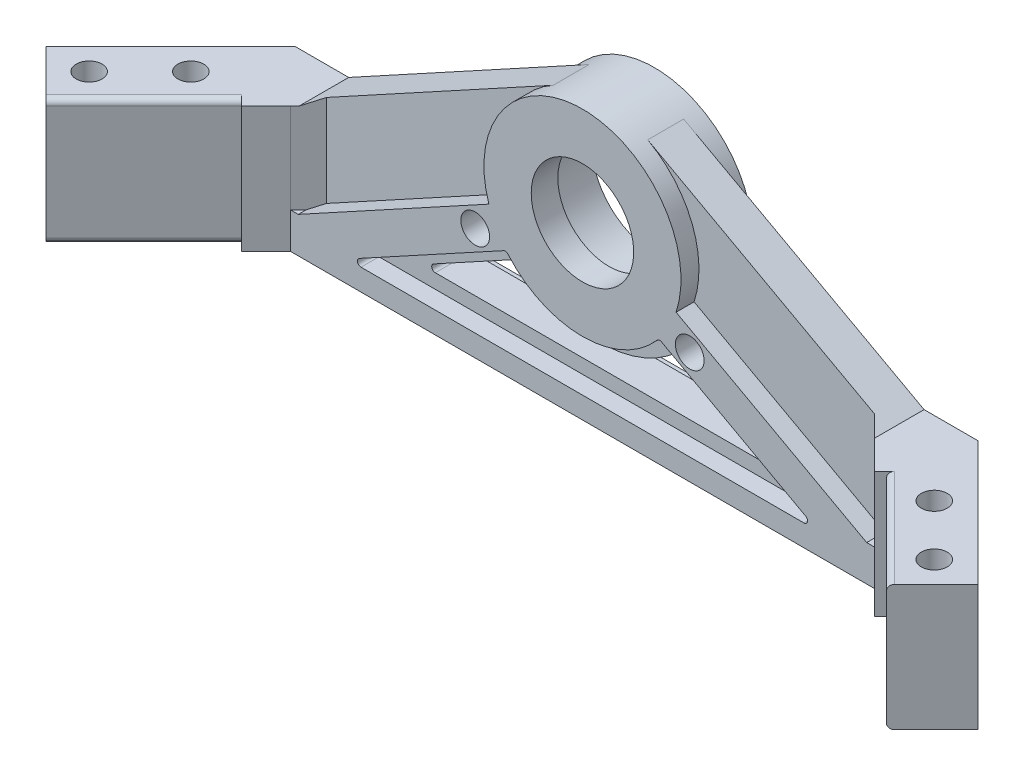
SolidWorks part; units mm, degrees
ref_plane "Front Plane" through (0, 0, 0) normal (0, 0, 1) x (1, 0, 0)
ref_plane "Top Plane" through (0, 0, 0) normal (0, 1, 0) x (1, 0, 0)
ref_plane "Right Plane" through (0, 0, 0) normal (1, 0, 0) x (0, 0, -1)
sketch "Sketch1" plane through (0, 0, 0) normal (0, 1, 0) x (-1, 0, 0)
  line L48 (74.9309, 32.5085) -> (74.2125, 33.2269)
  line L49 (74.2125, 33.2269) -> (56.9345, 15.9489)
  line L50 (57.6529, 15.2305) -> (56.9345, 15.9489)
  line L51 (-56.9345, 15.9489) -> (-74.2125, 33.2269)
  line L52 (-74.2125, 33.2269) -> (-74.9309, 32.5085)
  line L53 (-56.9345, 15.9489) -> (-57.6529, 15.2305)
  line L54 (-65.0167, 7.8667) -> (-61.5144, 4.3644)
  line L55 (-61.5144, 4.3644) -> (-52.3715, 13.5073)
  line L56 (-52.3715, 13.5073) -> (-55.8738, 17.0096)
  line L57 (-55.8738, 17.0096) -> (-65.0167, 7.8667)
  line L58 (55.8738, 17.0096) -> (52.3715, 13.5073)
  line L59 (52.3715, 13.5073) -> (61.5144, 4.3644)
  line L60 (61.5144, 4.3644) -> (65.0167, 7.8667)
  line L61 (65.0167, 7.8667) -> (55.8738, 17.0096)
  line L62 (17.3112, 9.525) -> (13.6482, 9.525)
  line L63 (17.3112, 12.7) -> (-17.3112, 12.7)
  line L64 (-13.6482, 9.525) -> (-17.3112, 9.525)
  line L65 (-17.3112, 3.175) -> (-13.6482, 3.175)
  line L66 (-17.3112, 0) -> (17.3112, 0)
  line L67 (13.6482, 3.175) -> (17.3112, 3.175)
  line L68 (-17.3112, 12.7) -> (-53.1788, 12.7)
  line L69 (-53.1788, 12.7) -> (-50.0038, 9.525)
  line L70 (-50.0038, 9.525) -> (-17.3112, 9.525)
  line L71 (-60.325, 3.175) -> (-57.15, 0)
  line L72 (-57.15, 0) -> (-17.3112, 0)
  line L73 (-17.3112, 3.175) -> (-60.325, 3.175)
  line L74 (17.3112, 9.525) -> (50.0038, 9.525)
  line L75 (50.0038, 9.525) -> (53.1788, 12.7)
  line L76 (53.1788, 12.7) -> (17.3112, 12.7)
  line L77 (57.15, 0) -> (60.325, 3.175)
  line L78 (60.325, 3.175) -> (17.3112, 3.175)
  line L79 (17.3112, 0) -> (57.15, 0)
  line L80 (-74.9309, 32.5085) -> (-82.2947, 25.1447)
  line L81 (-82.2947, 25.1447) -> (-65.0167, 7.8667)
  line L82 (-65.0167, 7.8667) -> (-57.6529, 15.2305)
  line L83 (-60.325, 3.175) -> (-13.6482, 3.175)
  line L84 (-13.6482, 9.525) -> (-50.0038, 9.525)
  line L85 (-50.0038, 9.525) -> (-53.1788, 12.7)
  line L86 (-53.1788, 12.7) -> (-61.5144, 4.3644)
  line L87 (-61.5144, 4.3644) -> (-60.325, 3.175)
  line L88 (13.6482, 3.175) -> (60.325, 3.175)
  line L89 (60.325, 3.175) -> (61.5144, 4.3644)
  line L90 (61.5144, 4.3644) -> (53.1788, 12.7)
  line L91 (53.1788, 12.7) -> (50.0038, 9.525)
  line L92 (50.0038, 9.525) -> (13.6482, 9.525)
  line L93 (82.2947, 25.1447) -> (74.9309, 32.5085)
  line L94 (57.6529, 15.2305) -> (65.0167, 7.8667)
  line L95 (65.0167, 7.8667) -> (82.2947, 25.1447)
sketch "Sketch3" plane through (0, 0, 0) normal (0, 1, 0) x (1, 0, 0)
  line L0 (-53.1788, -12.7) -> (-17.3112, -12.7) construction
  line L1 (-17.3112, 0) -> (-57.15, 0) construction
  line L2 (-57.15, 0) -> (-60.325, -3.175) construction
  line L3 (-60.325, -3.175) -> (-61.5144, -4.3644) construction
  line L4 (-61.5144, -4.3644) -> (-65.0167, -7.8667) construction
  line L5 (-74.2125, -33.2269) -> (-56.9345, -15.9489) construction
  line L6 (-74.9309, -32.5085) -> (-74.2125, -33.2269) construction
  line L7 (-82.2947, -25.1447) -> (-74.9309, -32.5085) construction
  line L8 (-65.0167, -7.8667) -> (-82.2947, -25.1447) construction
  line L9 (-51.5642, -12.7) -> (-17.3112, -12.7)
  line L10 (-17.3112, 0) -> (-57.15, 0)
  line L11 (-57.15, 0) -> (-60.325, -3.175)
  line L12 (-60.325, -3.175) -> (-61.5144, -4.3644)
  line L13 (-61.5144, -4.3644) -> (-65.0167, -7.8667)
  line L14 (-74.2125, -33.2269) -> (-56.9345, -15.9489)
  line L15 (-74.9309, -32.5085) -> (-74.2125, -33.2269)
  line L16 (-82.2947, -25.1447) -> (-74.9309, -32.5085)
  line L17 (-65.0167, -7.8667) -> (-82.2947, -25.1447)
  line L18 (0, 0) -> (0, -12.7) construction
  line L19 (-17.3112, -12.7) -> (17.3112, -12.7) construction
  line L20 (17.3112, 0) -> (-17.3112, 0) construction
  line L21 (-52.3715, -13.5073) -> (-61.5144, -4.3644) construction
  line L22 (-65.0167, -7.8667) -> (-55.8738, -17.0096) construction
  line L23 (-55.8738, -17.0096) -> (-52.3715, -13.5073) construction
  line L24 (17.3112, 0) -> (-17.3112, 0)
  line L25 (-17.3112, -12.7) -> (17.3112, -12.7)
  line L26 (-52.3715, -13.5073) -> (-61.5144, -4.3644)
  line L27 (-65.0167, -7.8667) -> (-55.8738, -17.0096)
  line L28 (-55.8738, -17.0096) -> (-52.3715, -13.5073)
  line L29 (55.8738, -17.0096) -> (52.3715, -13.5073)
  line L30 (65.0167, -7.8667) -> (55.8738, -17.0096)
  line L31 (52.3715, -13.5073) -> (61.5144, -4.3644)
  line L32 (65.0167, -7.8667) -> (82.2947, -25.1447)
  line L33 (82.2947, -25.1447) -> (74.9309, -32.5085)
  line L34 (74.9309, -32.5085) -> (74.2125, -33.2269)
  line L35 (74.2125, -33.2269) -> (56.9345, -15.9489)
  line L36 (61.5144, -4.3644) -> (65.0167, -7.8667)
  line L37 (60.325, -3.175) -> (61.5144, -4.3644)
  line L38 (57.15, 0) -> (60.325, -3.175)
  line L39 (17.3112, 0) -> (57.15, 0)
  line L40 (51.5642, -12.7) -> (17.3112, -12.7)
  line L41 (-52.3715, -13.5073) -> (-51.5642, -12.7)
  line L42 (52.3715, -13.5073) -> (51.5642, -12.7)
extrude "Boss-Extrude1" add sketch "Sketch3" along normal mid plane 22.225 contours L27 L17 L16 L15 L14 | L27 L28 L26 L13 | L18 L24 L10 L11 L12 L26 L41 L9 L25 | L24 L18 L25 L40 L42 L31 L37 L38 L39 | L36 L31 L29 L30 | L35 L34 L33 L32 L30 region at (-29.0802, 0, 6.2508) region at (-58.6941, 0, 10.687) region at (29.0802, 0, 6.2508) region at (-69.6146, 0, 20.5468) region at (58.6941, 0, 10.687) region at (69.6146, 0, 20.5468)
sketch "Sketch2" plane through (0, 0, 0) normal (0, 0, 1) x (1, 0, 0)
  line L0 (0, 0) -> (0, 36.45) construction
  line L1 (-17.3112, 0) -> (17.3112, 0) construction
  line L2 (50.8048, 11.1125) -> (8.3447, 34.3184)
  line L3 (-50.8048, 11.1125) -> (-8.3447, 34.3184)
  line L4 (50.8048, 11.1125) -> (15.4841, 11.1125)
  line L5 (57.15, 11.1125) -> (-57.15, 11.1125) construction
  line L6 (-50.8048, 11.1125) -> (-15.4841, 11.1125)
  circle A0 centre (0, 19.05) radius 11.05
  circle A1 centre (0, 19.05) radius 17.4
  circle A2 centre (0, 19.05) radius 9.05
  dimension "D1" = 22.1
  dimension "D2" = 6.35
  dimension "D4" = 2
  dimension "D3" = 19.05
extrude "Boss-Extrude2" add sketch "Sketch2" along normal up to surface (12.7 mm away) contours A1 L3 L6 | A1 L0 A0 | A0 L0 | L0 A0 | L0 A1 A0 | A1 L4 L2 | A2 region at (-8.8704, 4.5349, 0) region at (0.3891, 4.825, 0) region at (-10.8029, 19.05, 0) region at (0.2471, 9, 0) region at (-27.6614, 17.7256, 0) region at (27.6614, 17.7256, 0) up to face at (0, 0, 12.7)
extrude "Cut-Extrude2" cut sketch "Sketch2<3>" along normal blind 8 contours A0 L0 A2 | A2 L0 | L0 A2 | L0 A0 A2 region at (-10.8029, 19.05, 0) region at (0.2471, 9, 0) region at (-3.8409, 19.05, 0) region at (3.8409, 19.05, 0)
sketch "Sketch2<3>" plane through (0, 0, 0) normal (0, 0, 1) x (1, 0, 0) same geometry as "Sketch2"
extrude "Cut-Extrude3" cut sketch "Sketch2<5>" along normal through all contours A2 L0 | L0 A2 region at (-3.8409, 19.05, 0) region at (3.8409, 19.05, 0)
sketch "Sketch2<5>" plane through (0, 0, 0) normal (0, 0, 1) x (1, 0, 0) same geometry as "Sketch2"
sketch "Sketch5" plane through (0, 0, 0) normal (0, 0, -1) x (-1, 0, 0)
  line L0 (-16.5348, 13.6314) -> (-57.15, -8.5663)
  line L1 (-48.5682, -11.1125) -> (-13.4894, 8.0593)
  line L2 (0, 19.05) -> (-55.1885, -11.1125) construction
  line L3 (0, 19.05) -> (0, -11.1125) construction
  line L4 (16.5348, 13.6314) -> (57.15, -8.5663)
  line L5 (48.5682, -11.1125) -> (13.4894, 8.0593)
  line L6 (0, 19.05) -> (55.1885, -11.1125) construction
  line L7 (57.15, 11.1125) -> (50.8048, 11.1125)
  line L8 (50.8048, 11.1125) -> (8.3447, 34.3184)
  line L9 (-8.3447, 34.3184) -> (-50.8048, 11.1125)
  line L10 (-50.8048, 11.1125) -> (-57.15, 11.1125)
  line L11 (-57.15, 11.1125) -> (-57.15, -11.1125)
  line L12 (-57.15, -11.1125) -> (57.15, -11.1125)
  line L13 (57.15, -11.1125) -> (57.15, 11.1125)
  line L14 (57.15, 11.1125) -> (50.8048, 11.1125)
  line L15 (50.8048, 11.1125) -> (8.3447, 34.3184)
  line L16 (-8.3447, 34.3184) -> (-50.8048, 11.1125)
  line L17 (-50.8048, 11.1125) -> (-57.15, 11.1125)
  line L18 (-57.15, 11.1125) -> (-57.15, -11.1125)
  line L19 (-57.15, -11.1125) -> (57.15, -11.1125)
  line L20 (57.15, -11.1125) -> (57.15, 11.1125)
  line L21 (-41.597, -7.3025) -> (41.597, -7.3025)
  line L22 (-31.6533, -4.7625) -> (31.6533, -4.7625)
  line L23 (-31.6533, -4.7625) -> (-14.0224, 4.8734)
  line L24 (31.6533, -4.7625) -> (14.0224, 4.8734)
  line L25 (-57.15, 11.1125) -> (-82.2947, 11.1125)
  line L26 (-82.2947, 11.1125) -> (-82.2947, -11.1125)
  line L27 (-82.2947, -11.1125) -> (-57.15, -11.1125)
  line L28 (-82.2947, -4.7625) -> (-50.1902, -4.7625)
  line L29 (82.2947, -4.7625) -> (50.1902, -4.7625)
  line L33 (57.15, -11.1125) -> (82.2947, -11.1125)
  line L34 (82.2947, -11.1125) -> (82.2947, 11.1125)
  line L35 (82.2947, 11.1125) -> (57.15, 11.1125)
  line L36 (57.15, 11.1125) -> (57.15, -11.1125)
  line L37 (57.15, -11.1125) -> (82.2947, -11.1125)
  line L38 (82.2947, -11.1125) -> (82.2947, 11.1125)
  line L39 (82.2947, 11.1125) -> (57.15, 11.1125)
  line L40 (57.15, 11.1125) -> (57.15, -11.1125)
  circle A0 centre (0, 19.05) radius 11.05 construction
  arc A1 (8.3447, 34.3184) -> (-8.3447, 34.3184) centre (0, 19.05) ccw
  arc A2 (8.3447, 34.3184) -> (-8.3447, 34.3184) centre (0, 19.05) ccw
  circle A3 centre (0, 19.05) radius 11.05
  circle A4 centre (0, 19.05) radius 17.4
  arc A5 (-14.0224, 4.8734) -> (14.0224, 4.8734) centre (0, 19.05) ccw
  circle A6 centre (0, 19.05) radius 19.94 construction
  line M30 (57.15, 11.1125) -> (50.8048, 11.1125)
  line M31 (50.8048, 11.1125) -> (8.3447, 34.3184)
  line M33 (-8.3447, 34.3184) -> (-50.8048, 11.1125)
  line M34 (-50.8048, 11.1125) -> (-57.15, 11.1125)
  line M35 (-57.15, 11.1125) -> (-57.15, -11.1125)
  dimension "D2" = 3.175
  dimension "D3" = 3.175
  dimension "D4" = 3.81
  dimension "D6" = 2.54
  dimension "D7" = 2.54
  dimension "D9" = 6.35
  dimension "D1" = 0
  dimension "D5" = 2.54
  dimension "D8" = 0
extrude "Cut-Extrude4" cut sketch "Sketch5" against normal blind 3.175 contours L26 L28 L25 M35 | A4 L28 L0 M33 M34 M35 | A4 L4 L29 L20 M30 M31 | L38 L39 L20 L29 | A4 L1 L21 L5 L23 A5 L24 L22 region at (36.5899, 11.2064, 0) region at (0, 0.804, 0) region at (69.7224, 3.175, 0) region at (-36.5899, 11.2064, 0) region at (-69.7224, 3.175, 0)
extrude "Cut-Extrude5" cut sketch "Sketch5<3>" against normal through all contours A5 L23 L22 L24 region at (0, -1.6144, 0)
sketch "Sketch5<3>" plane through (0, 0, 0) normal (0, 0, -1) x (-1, 0, 0) same geometry as "Sketch5"
sketch "Sketch6" plane through (0, 0, 0) normal (0, 0, -1) x (-1, 0, 0)
  line L0 (0, 19.05) -> (-18.9451, 8.6958) construction
  line L1 (-16.5348, 13.6314) -> (-50.1902, -4.7625) construction
  line L2 (0, 19.05) -> (0, 0) construction
  circle A0 centre (0, 19.05) radius 11.05 construction
  circle A1 centre (0, 19.05) radius 11.05 construction
  circle A2 centre (-18.9451, 8.6958) radius 2.54
  circle A3 centre (18.9451, 8.6958) radius 2.54
  dimension "D2" = 5.08
  dimension "D1" = 21.59
extrude "Cut-Extrude6" cut sketch "Sketch6" against normal through all contours A2 | A3 region at (18.9451, 8.6958, 0) region at (-18.9451, 8.6958, 0)
sketch "Sketch7" plane through (0, 0, 12.7) normal (0, 0, 1) x (1, 0, 0)
  line L0 (0, 19.05) -> (-51.5642, -9.1317) construction
  line L1 (0, 19.05) -> (0, 0) construction
  line L2 (0, 19.05) -> (51.5642, -9.1317) construction
  line L3 (-51.5642, -5.5134) -> (-8.9593, 17.7717)
  line L4 (-50.1902, -4.7625) -> (-51.5642, -4.7625)
  line L5 (-48.5189, -11.0856) -> (-5.9139, 12.1996)
  line L6 (48.5189, -11.0856) -> (5.9139, 12.1996)
  line L7 (51.5642, 11.1125) -> (50.8048, 11.1125)
  line L8 (50.8048, 11.1125) -> (8.3447, 34.3184)
  line L9 (-8.3447, 34.3184) -> (-50.8048, 11.1125)
  line L10 (-50.8048, 11.1125) -> (-51.5642, 11.1125)
  line L11 (-51.5642, 11.1125) -> (-51.5642, -11.1125)
  line L12 (-51.5642, -11.1125) -> (51.5642, -11.1125)
  line L13 (51.5642, -11.1125) -> (51.5642, 11.1125)
  line L14 (51.5642, 11.1125) -> (50.8048, 11.1125)
  line L15 (50.8048, 11.1125) -> (8.3447, 34.3184)
  line L16 (-8.3447, 34.3184) -> (-50.8048, 11.1125)
  line L17 (-50.8048, 11.1125) -> (-51.5642, 11.1125)
  line L18 (-51.5642, 11.1125) -> (-51.5642, -11.1125)
  line L19 (-51.5642, -11.1125) -> (51.5642, -11.1125)
  line L20 (51.5642, -11.1125) -> (51.5642, 11.1125)
  line L21 (50.1902, -4.7625) -> (51.5642, -4.7625)
  line L22 (51.5642, -5.5134) -> (8.9593, 17.7717)
  line L23 (-41.597, -7.3025) -> (41.597, -7.3025)
  circle A0 centre (0, 19.05) radius 9.05 construction
  arc A1 (8.3447, 34.3184) -> (-8.3447, 34.3184) centre (0, 19.05) ccw
  arc A2 (8.3447, 34.3184) -> (-8.3447, 34.3184) centre (0, 19.05) ccw
  circle A3 centre (0, 19.05) radius 9.05
  circle A4 centre (0, 19.05) radius 9.05
  circle A8 centre (0, 19.05) radius 17.4
  arc M19 (-14.0224, 4.8734) -> (14.0224, 4.8734) centre (0, 19.05) ccw
  line M21 (14.0224, 4.8734) -> (31.6533, -4.7625)
  line M23 (31.6533, -4.7625) -> (-31.6533, -4.7625)
  line M25 (-31.6533, -4.7625) -> (-14.0224, 4.8734)
  line M28 (51.5642, 11.1125) -> (50.8048, 11.1125)
  line M29 (50.8048, 11.1125) -> (8.3447, 34.3184)
  line M31 (-8.3447, 34.3184) -> (-50.8048, 11.1125)
  line M32 (-50.8048, 11.1125) -> (-51.5642, 11.1125)
  line M33 (-51.5642, 11.1125) -> (-51.5642, -11.1125)
  dimension "D2" = 6.35
  dimension "D3" = 6.35
  dimension "D4" = 3.81
  dimension "D1" = 0
extrude "Cut-Extrude7" cut sketch "Sketch7" against normal blind 3.175 contours A8 L5 L23 L6 M19 M21 M23 M25 | A8 L4 L3 M31 M32 M33 | A8 L22 L21 L20 M28 M29 region at (-33.839, 12.4499, 12.7) region at (0, 0.804, 12.7) region at (33.839, 12.4499, 12.7)
chamfer "Chamfer1" distance 3.175 angle 45 2 edges at (51.5642, 3.175, 9.525) (-51.5642, 3.175, 9.525)
fillet "Fillet1" radius 0.635 12 edges at (-41.597, -7.3025, 1.5875) (41.597, -7.3025, 1.5875) (13.4894, 8.0593, 1.5875) (-13.4894, 8.0593, 1.5875) (14.0224, 4.8734, 6.35) (-14.0224, 4.8734, 6.35) (-31.6533, -4.7625, 6.35) (31.6533, -4.7625, 6.35) (41.597, -7.3025, 11.1125) (-41.597, -7.3025, 11.1125) (13.4894, 8.0593, 11.1125) (-13.4894, 8.0593, 11.1125)
fillet "Fillet3" radius 1.016 4 edges at (-65.5735, -11.1125, 24.5879) (65.5735, -11.1125, 24.5879) (-65.5735, 11.1125, 24.5879) (65.5735, 11.1125, 24.5879)
sketch "Sketch8" plane through (0, 11.1125, 0) normal (0, 1, 0) x (1, 0, 0)
  line L0 (57.6529, -15.2305) -> (55.8738, -17.0096) construction
  line L1 (57.6529, -15.2305) -> (55.8738, -17.0096)
  line L2 (0, 0) -> (0, -12.7) construction
  line L3 (17.4, 0) -> (-17.4, 0) construction
  line L4 (-17.4, -12.7) -> (17.4, -12.7) construction
  line L5 (57.6529, -15.2305) -> (65.0167, -7.8667)
  line L6 (60.325, -3.175) -> (82.2947, -25.1447) construction
  line L7 (61.1552, -11.7282) -> (78.4332, -29.0062) construction
  line L8 (82.2947, -25.1447) -> (74.9309, -32.5085) construction
  line L10 (-57.6529, -15.2305) -> (-55.8738, -17.0096)
  line L11 (-57.6529, -15.2305) -> (-65.0167, -7.8667)
  line L12 (-61.1552, -11.7282) -> (-78.4332, -29.0062) construction
  circle A0 centre (65.6453, -16.2183) radius 2.286
  circle A1 centre (74.6256, -25.1986) radius 2.286
  circle A2 centre (-65.6453, -16.2183) radius 2.286
  circle A3 centre (-74.6256, -25.1986) radius 2.286
  dimension "D2" = 4.572
  dimension "D3" = 4.572
  dimension "D1" = 5.461
  dimension "D4" = 6.35
  dimension "D5" = 12.7
extrude "Cut-Extrude8" cut sketch "Sketch8" against normal through all contours A1 | A3 | A0 | A2 region at (74.6256, 11.1125, 25.1986) region at (-74.6256, 11.1125, 25.1986)
sketch "Sketch9" plane through (0, -11.1125, 0) normal (0, -1, 0) x (1, 0, 0)
  line L0 (0, 0) -> (0, 12.7) construction
  line L1 (-51.5642, 12.7) -> (51.5642, 12.7) construction
  line L2 (63.5, 6.35) -> (-63.5, 6.35) construction
  line L3 (-57.15, 0) -> (-82.2947, 25.1447) construction
  text T0 "<b>SN101</b>"
  point P10 (0, 6.35)
extrude "Cut-Extrude9" cut sketch "Sketch9" against normal blind 0.5
